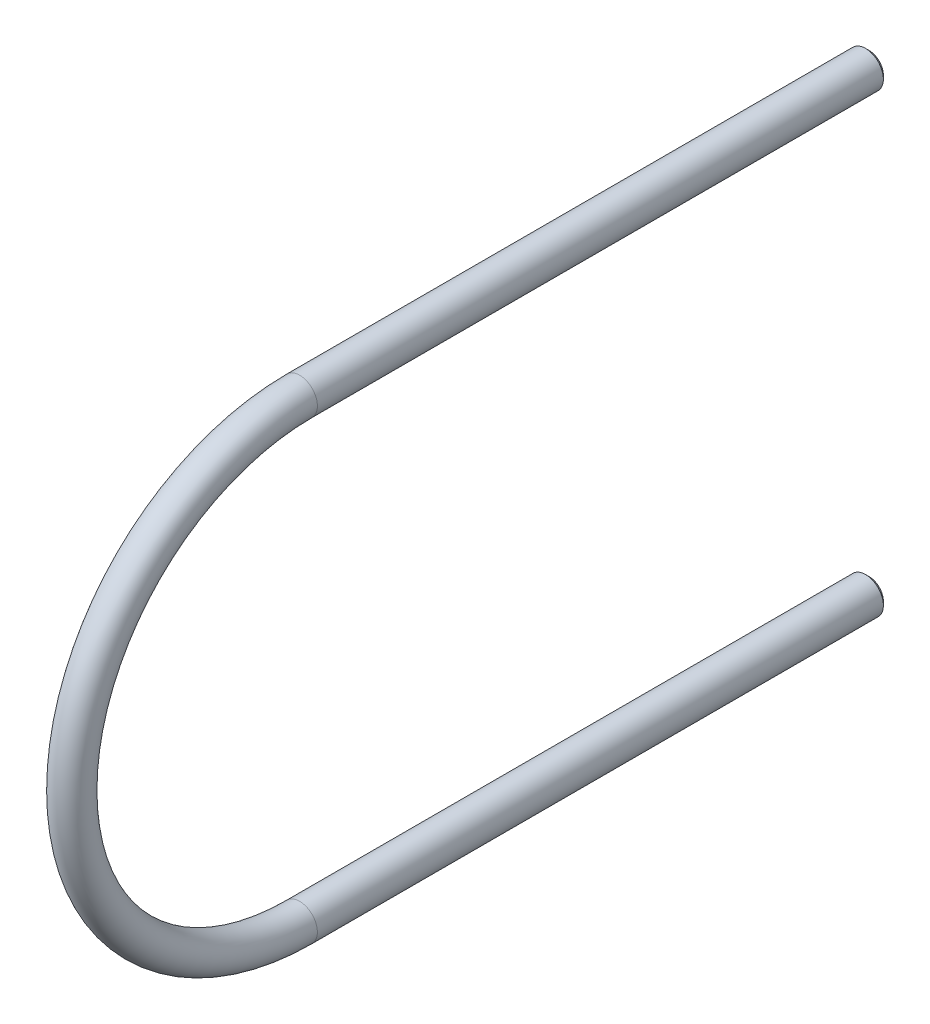
SolidWorks part; units mm, degrees
ref_plane "Front Plane" through (0, 0, 0) normal (0, 0, 1) x (1, 0, 0)
ref_plane "Top Plane" through (0, 0, 0) normal (0, 1, 0) x (1, 0, 0)
ref_plane "Right Plane" through (0, 0, 0) normal (1, 0, 0) x (0, 0, -1)
sketch "Sketch1" plane through (0, 0, 0) normal (0, 0, 1) x (1, 0, 0)
  line L0 (0, 0) -> (0, 32) construction
  line L1 (0, 0) -> (36, 0) construction
  circle A1 centre (0, 32) radius 2.5
revolve "Revolve1" add sketch "Sketch1" angle 180 about L1
extrude "Boss-Extrude1" add sketch "Sketch1<2>" against normal blind 80
sketch "Sketch1<2>" plane through (0, 0, 0) normal (0, 0, 1) x (1, 0, 0) same geometry as "Sketch1"
sketch "Sketch2" plane through (0, 0, 0) normal (0, 0, -1) x (-1, 0, 0)
  circle A0 centre (0, -32) radius 2.5
extrude "Boss-Extrude2" add sketch "Sketch2" along normal blind 80
chamfer "Chamfer1" distance 0.5 angle 45 2 edges at (0, -29.5, -80) (2.5, 32, -80)
